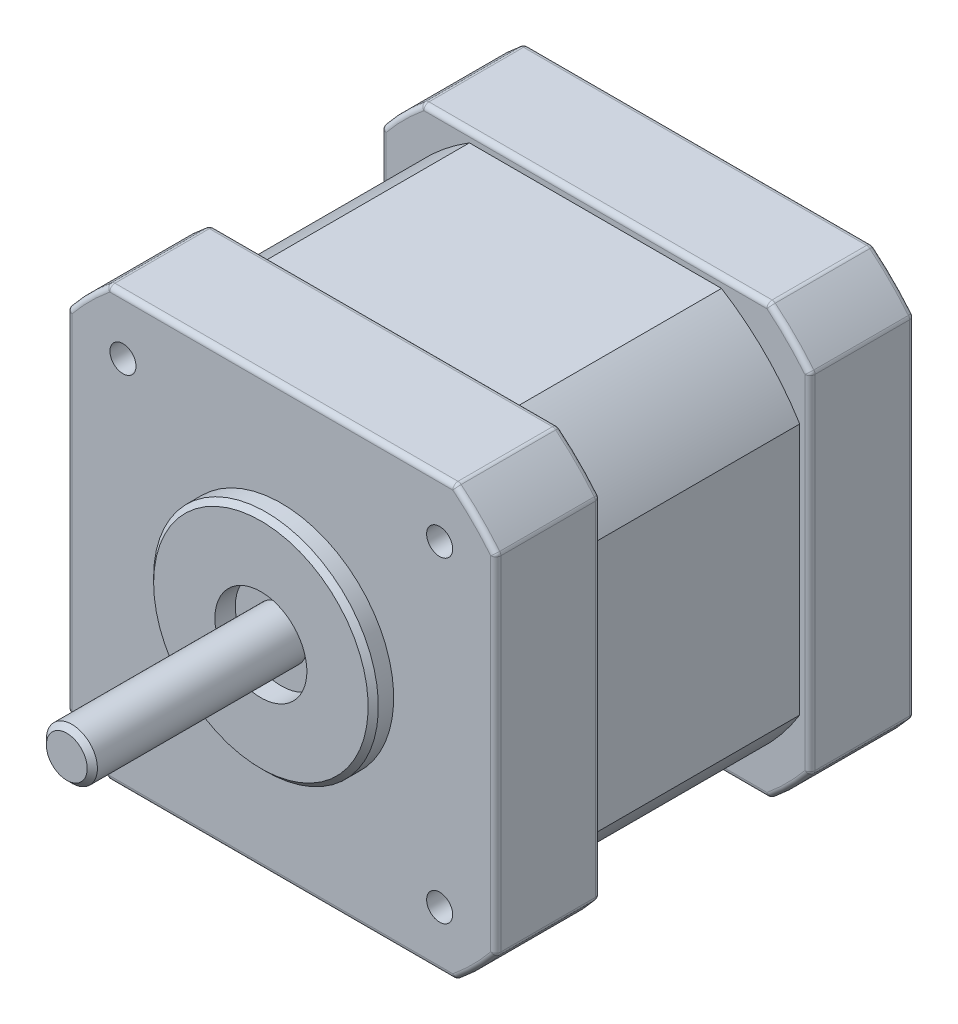
SolidWorks part; units mm, degrees
ref_plane "前视基准面" through (0, 0, 0) normal (0, 0, 1) x (1, 0, 0)
ref_plane "上视基准面" through (0, 0, 0) normal (0, 1, 0) x (1, 0, 0)
ref_plane "右视基准面" through (0, 0, 0) normal (1, 0, 0) x (0, 0, -1)
sketch "草图1" plane through (0, 0, 0) normal (1, 0, 0) x (0, 0, -1)
  line L0 (-66.5282, 0) -> (63.5561, 0) construction
  line L1 (0, 75.6729) -> (0, -67.6713) construction
  line L2 (0, 0) -> (0, 2)
  line L3 (0.5, 2.5) -> (21, 2.5)
  line L4 (19, 10.5) -> (19, 4.5)
  line L5 (19.5, 11) -> (21, 11)
  line L6 (21, 11) -> (21, 21)
  line L7 (21, 21) -> (31.25, 21)
  line L8 (31.25, 21) -> (51.75, 21)
  line L9 (51.75, 21) -> (62, 21)
  line L10 (62, 21) -> (62, 0)
  line L11 (19, 4.5) -> (21, 4.5)
  line L12 (21, 4.5) -> (21, 2.5)
  line L13 (0, 2) -> (0.5, 2.5)
  line L14 (19.5, 11) -> (19, 10.5)
  point P6 (0, 2.5)
  point P9 (19, 11)
  dimension "D1" = 2
  dimension "D2" = 21
  dimension "D3" = 41
  dimension "D4" = 5
  dimension "D5" = 22
  dimension "D6" = 2
  dimension "D7" = 20.5
  dimension "D8" = 10.25
  dimension "D9" = 42
sketch "草图2" plane through (0, 0, 0) normal (0, 0, 1) x (1, 0, 0)
  line L0 (0, 86.6855) -> (0, -75.8244) construction
  line L1 (21, -21) -> (-21, -21)
  line L2 (21, -21) -> (21, 21)
  line L3 (21, 21) -> (-21, 21)
  line L4 (-21, -21) -> (-21, 21)
  line L5 (21, -21) -> (-21, 21) construction
  line L6 (21, 21) -> (-21, -21) construction
  line L7 (-67.4344, 0) -> (53.3757, 0) construction
  circle A0 centre (-15.5, 15.5) radius 1.275
  arc A1 (21, 16.9706) -> (16.9706, 21) centre (0, 0) ccw
  circle A2 centre (15.5, 15.5) radius 1.275
  circle A3 centre (15.5, -15.5) radius 1.275
  circle A4 centre (-15.5, -15.5) radius 1.275
  arc A5 (16.9706, -21) -> (21, -16.9706) centre (0, 0) ccw
  arc A6 (-21, -16.9706) -> (-16.9706, -21) centre (0, 0) ccw
  arc A7 (-16.9706, 21) -> (-21, 16.9706) centre (0, 0) ccw
  point P0 (0, 0)
  dimension "D4" = 2.55
  dimension "D5" = 54
  dimension "D1" = 42
  dimension "D2" = 42
  dimension "D3" = 31
sketch "草图3" plane through (0, 0, 0) normal (1, 0, 0) x (0, 0, -1)
  line L0 (0, 0) -> (0, 2) construction
  line L1 (0, 2) -> (0.5, 2.5) construction
  line L2 (0.5, 2.5) -> (21, 2.5) construction
  line L3 (21, 4.5) -> (21, 2.5) construction
  line L4 (19, 4.5) -> (21, 4.5) construction
  line L5 (19, 10.5) -> (19, 4.5) construction
  line L6 (19.5, 11) -> (19, 10.5) construction
  line L7 (19.5, 11) -> (21, 11) construction
  line L8 (0, 0) -> (0, 2)
  line L9 (0, 2) -> (0.5, 2.5)
  line L10 (0.5, 2.5) -> (21, 2.5)
  line L11 (21, 4.5) -> (21, 2.5)
  line L12 (19, 4.5) -> (21, 4.5)
  line L13 (19, 10.5) -> (19, 4.5)
  line L14 (19.5, 11) -> (19, 10.5)
  line L15 (19.5, 11) -> (21, 11)
  line L16 (21, 11) -> (21, 0)
  line L17 (-66.5282, 0) -> (63.5561, 0) construction
  line L18 (21, 0) -> (0, 0)
revolve "旋转1" add sketch "草图3" angle 360 about L18 region at (0, 7.7201, -20.0081) region at (0, 1.2474, -10.5247)
sketch "草图4" plane through (0, 0, 0) normal (0, 0, 1) x (1, 0, 0)
  line L0 (21, 21) -> (-21, 21) construction
  line L1 (-21, -21) -> (-21, 21) construction
  line L2 (21, -21) -> (-21, -21) construction
  line L3 (21, -21) -> (21, 21) construction
  line L4 (16.9706, 21) -> (-16.9706, 21)
  line L5 (-21, -16.9706) -> (-21, 16.9706)
  line L6 (16.9706, -21) -> (-16.9706, -21)
  line L7 (21, -16.9706) -> (21, 16.9706)
  arc A0 (21, 16.9706) -> (16.9706, 21) centre (0, 0) ccw construction
  arc A1 (-16.9706, 21) -> (-21, 16.9706) centre (0, 0) ccw construction
  arc A2 (-21, -16.9706) -> (-16.9706, -21) centre (0, 0) ccw construction
  arc A3 (16.9706, -21) -> (21, -16.9706) centre (0, 0) ccw construction
  arc A4 (21, 16.9706) -> (16.9706, 21) centre (0, 0) ccw
  arc A5 (-16.9706, 21) -> (-21, 16.9706) centre (0, 0) ccw
  arc A6 (-21, -16.9706) -> (-16.9706, -21) centre (0, 0) ccw
  arc A7 (16.9706, -21) -> (21, -16.9706) centre (0, 0) ccw
extrude "凸台-拉伸1" add sketch "草图4" against normal up to vertex (31.25 mm away) from vertex up to point (0, 21, -31.25) starting at point (0, 21, -21)
extrude "凸台-拉伸2" add sketch "草图4<2>" against normal up to vertex (62 mm away) from vertex separate body up to point (0, 21, -62) starting at point (0, 21, -51.75)
sketch "草图4<2>" plane through (0, 0, 0) normal (0, 0, 1) x (1, 0, 0) same geometry as "草图4"
sketch "草图5" plane through (0, 0, 0) normal (0, 0, 1) x (1, 0, 0)
  line L0 (21, 21) -> (-21, 21) construction
  line L1 (-21, -21) -> (-21, 21) construction
  line L2 (21, -21) -> (-21, -21) construction
  line L3 (21, -21) -> (21, 21) construction
  line L4 (12.6194, 21) -> (-12.6194, 21)
  line L5 (-21, -12.6194) -> (-21, 12.6194)
  line L6 (12.6194, -21) -> (-12.6194, -21)
  line L7 (21, -12.6194) -> (21, 12.6194)
  line L8 (12.339, 20) -> (-12.339, 20)
  line L9 (-20, -12.339) -> (-20, 12.339)
  line L10 (12.339, -20) -> (-12.339, -20)
  line L11 (20, -12.339) -> (20, 12.339)
  arc A0 (-12.6194, 21) -> (-21, 12.6194) centre (0, 0) ccw
  arc A1 (21, 12.6194) -> (12.6194, 21) centre (0, 0) ccw
  arc A2 (12.6194, -21) -> (21, -12.6194) centre (0, 0) ccw
  arc A3 (-21, -12.6194) -> (-12.6194, -21) centre (0, 0) ccw
  arc A4 (-12.339, 20) -> (-20, 12.339) centre (0, 0) ccw
  arc A5 (-20, -12.339) -> (-12.339, -20) centre (0, 0) ccw
  arc A6 (12.339, -20) -> (20, -12.339) centre (0, 0) ccw
  arc A7 (20, 12.339) -> (12.339, 20) centre (0, 0) ccw
  dimension "D1" = 49
  dimension "D2" = 1
extrude "凸台-拉伸3" add sketch "草图5" against normal up to vertex (51.75 mm away) from vertex contours L11 A7 L8 A4 L9 A5 L10 A6 region at (0, 0, 0) up to point (0, 21, -51.75) starting at point (0, 21, -31.25)
sketch "草图7" plane through (0, 0, 0) normal (0, 0, 1) x (1, 0, 0)
  circle A0 centre (-15.5, 15.5) radius 1.275 construction
  circle A1 centre (15.5, 15.5) radius 1.275 construction
  circle A2 centre (15.5, -15.5) radius 1.275 construction
  circle A3 centre (-15.5, -15.5) radius 1.275 construction
  circle A4 centre (-15.5, 15.5) radius 1.275
  circle A5 centre (15.5, 15.5) radius 1.275
  circle A6 centre (15.5, -15.5) radius 1.275
  circle A7 centre (-15.5, -15.5) radius 1.275
extrude "切除-拉伸4" cut sketch "草图7" against normal blind 5 from vertex starting at point (0, 21, -21)
cosmetic thread "装饰螺纹线1" parameters "D2"=3
cosmetic thread "装饰螺纹线2" parameters "D2"=3
cosmetic thread "装饰螺纹线3" parameters "D2"=3
cosmetic thread "装饰螺纹线4" parameters "D2"=3
fillet "圆角1" radius 0.5 24 edges at (-19.0919, 19.0919, -31.25) (-21, 0, -31.25) (-19.0919, -19.0919, -31.25) (0, -21, -31.25) (19.0919, -19.0919, -31.25) (21, 0, -31.25) (19.0919, 19.0919, -31.25) (0, 21, -31.25) (-19.0919, 19.0919, -21) (-21, 0, -21) (-19.0919, -19.0919, -21) (0, -21, -21) (19.0919, -19.0919, -21) (21, 0, -21) (19.0919, 19.0919, -21) (0, 21, -21) (21, -16.9706, -26.125) (16.9706, -21, -26.125) (-16.9706, -21, -26.125) (-21, -16.9706, -26.125) (-16.9706, 21, -26.125) (-21, 16.9706, -26.125) (21, 16.9706, -26.125) (16.9706, 21, -26.125)
fillet "圆角2" radius 0.5 24 edges at (0, 21, -62) (-19.0919, 19.0919, -62) (-21, 0, -62) (-19.0919, -19.0919, -62) (0, -21, -62) (19.0919, -19.0919, -62) (21, 0, -62) (19.0919, 19.0919, -62) (19.0919, -19.0919, -51.75) (0, -21, -51.75) (-19.0919, -19.0919, -51.75) (-21, 0, -51.75) (-19.0919, 19.0919, -51.75) (21, 0, -51.75) (19.0919, 19.0919, -51.75) (0, 21, -51.75) (-16.9706, -21, -56.875) (-21, -16.9706, -56.875) (21, -16.9706, -56.875) (16.9706, -21, -56.875) (21, 16.9706, -56.875) (16.9706, 21, -56.875) (-16.9706, 21, -56.875) (-21, 16.9706, -56.875)
